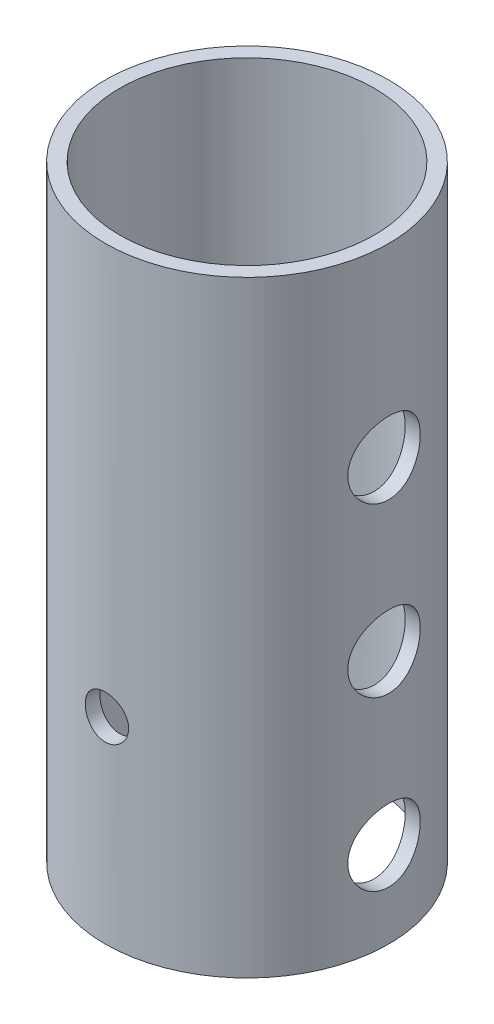
SolidWorks part; units mm, degrees
material "PTFE (general)"
ref_plane "Front Plane" through (0, 0, 0) normal (0, 0, 1) x (1, 0, 0)
ref_plane "Top Plane" through (0, 0, 0) normal (0, 1, 0) x (1, 0, 0)
ref_plane "Right Plane" through (0, 0, 0) normal (1, 0, 0) x (0, 0, -1)
sketch "Sketch1" plane through (0, 0, 0) normal (0, 1, 0) x (1, 0, 0)
  circle A0 centre (0, 0) radius 49
  circle A1 centre (0, 0) radius 44
  dimension "D1" = 98
  dimension "D2" = 88
extrude "Boss-Extrude1" add sketch "Sketch1" along normal blind 209.8
sketch "Sketch2" plane through (0, 0, 0) normal (1, 0, 0) x (0, 0, -1)
  line L0 (44, 209.8) -> (-44, 209.8) construction
  circle A0 centre (0, 145.6) radius 12.53
  circle A1 centre (0, 87.6) radius 12.53
  circle A2 centre (0, 29.6) radius 12.53
  dimension "D2" = 25.06
  dimension "D3" = 25.06
  dimension "D4" = 25.06
  dimension "D1" = 64.2
  dimension "D5" = 58
  dimension "D6" = 58
extrude "Cut-Extrude1" cut sketch "Sketch2" along normal through all
sketch "Sketch4" plane through (0, 0, 0) normal (0, 0, 1) x (1, 0, 0)
  line L0 (-49, 0) -> (49, 0) construction
  circle A0 centre (0, 68) radius 7.5
  dimension "D1" = 15
  dimension "D2" = 68
extrude "Cut-Extrude2" cut sketch "Sketch4" along normal through all
sketch "Sketch5" plane through (0, 0, 0) normal (0, 0, 1) x (1, 0, 0)
  line L0 (49, 209.8) -> (-49, 209.8) construction
  circle A0 centre (0, 141.8) radius 7.5
  dimension "D1" = 15
  dimension "D2" = 68
extrude "Cut-Extrude3" cut sketch "Sketch5" against normal through all
